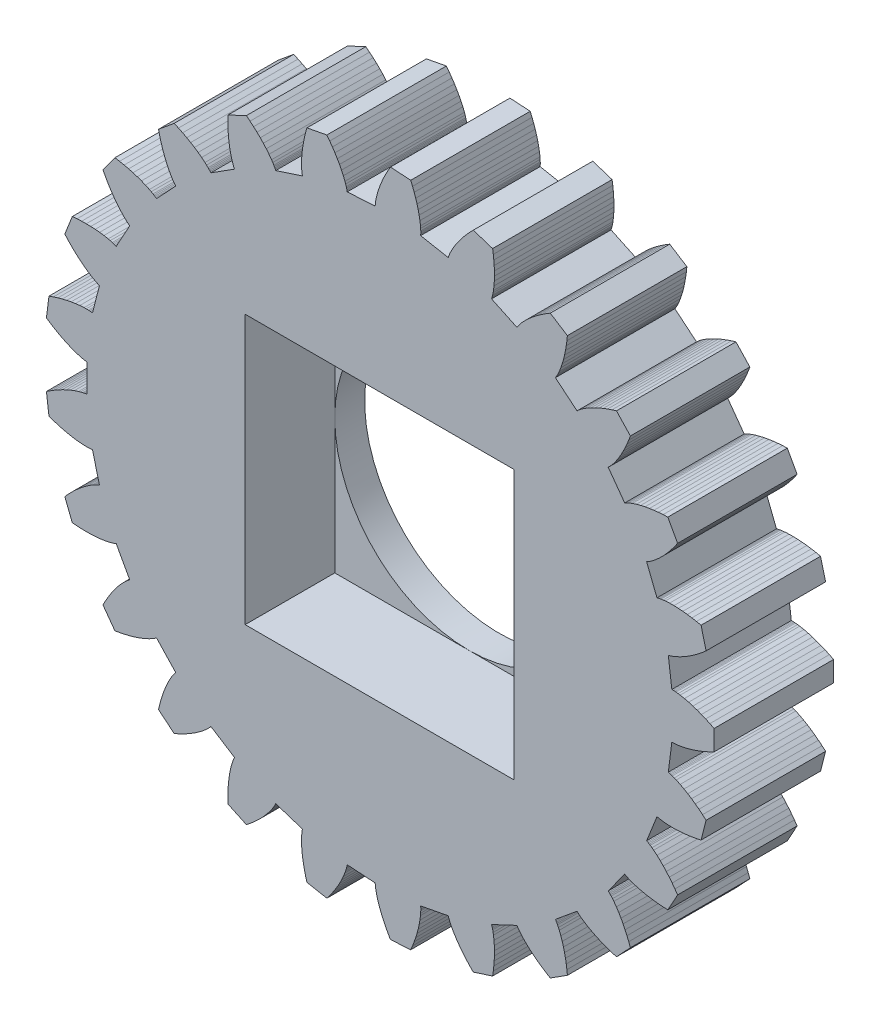
SolidWorks part; units mm, degrees
ref_plane "Front Plane" through (0, 0, 0) normal (0, 0, 1) x (1, 0, 0)
ref_plane "Top Plane" through (0, 0, 0) normal (0, 1, 0) x (1, 0, 0)
ref_plane "Right Plane" through (0, 0, 0) normal (1, 0, 0) x (0, 0, -1)
sketch "Model" plane through (0, 0, 0) normal (0, 0, 1) x (1, 0, 0)
  line L0 (22.5153, 13.4937) -> (22.5501, 13.4944)
  line L1 (22.5501, 13.4944) -> (22.5851, 13.4936)
  line L2 (22.5851, 13.4936) -> (22.6201, 13.4916)
  line L3 (22.6201, 13.4916) -> (22.6552, 13.4888)
  line L4 (22.6552, 13.4888) -> (22.7255, 13.481)
  line L5 (22.7255, 13.481) -> (22.796, 13.4706)
  line L6 (22.796, 13.4706) -> (22.9373, 13.4433)
  line L7 (22.9373, 13.4433) -> (23.079, 13.4085)
  line L8 (23.079, 13.4085) -> (23.221, 13.3669)
  line L9 (23.221, 13.3669) -> (23.363, 13.3191)
  line L10 (23.363, 13.3191) -> (23.5051, 13.2655)
  line L11 (23.5051, 13.2655) -> (23.647, 13.2062)
  line L12 (23.647, 13.2062) -> (23.7888, 13.1416)
  line L13 (23.7888, 13.1416) -> (23.9303, 13.0718)
  line L14 (23.9303, 13.0718) -> (23.9303, 12.3915)
  line L15 (23.9303, 12.3915) -> (23.7888, 12.3217)
  line L16 (23.7888, 12.3217) -> (23.647, 12.257)
  line L17 (23.647, 12.257) -> (23.5051, 12.1978)
  line L18 (23.5051, 12.1978) -> (23.363, 12.1441)
  line L19 (23.363, 12.1441) -> (23.221, 12.0963)
  line L20 (23.221, 12.0963) -> (23.079, 12.0548)
  line L21 (23.079, 12.0548) -> (22.9373, 12.0199)
  line L22 (22.9373, 12.0199) -> (22.796, 11.9927)
  line L23 (22.796, 11.9927) -> (22.7255, 11.9823)
  line L24 (22.7255, 11.9823) -> (22.6552, 11.9745)
  line L25 (22.6552, 11.9745) -> (22.6201, 11.9716)
  line L26 (22.6201, 11.9716) -> (22.5851, 11.9697)
  line L27 (22.5851, 11.9697) -> (22.5501, 11.9688)
  line L28 (22.5501, 11.9688) -> (22.5153, 11.9696)
  line L29 (22.5153, 11.9696) -> (22.3975, 11.0367)
  line L30 (22.3975, 11.0367) -> (22.4314, 11.0287)
  line L31 (22.4314, 11.0287) -> (22.465, 11.0192)
  line L32 (22.465, 11.0192) -> (22.4984, 11.0086)
  line L33 (22.4984, 11.0086) -> (22.5317, 10.9971)
  line L34 (22.5317, 10.9971) -> (22.5978, 10.9721)
  line L35 (22.5978, 10.9721) -> (22.6635, 10.9445)
  line L36 (22.6635, 10.9445) -> (22.7937, 10.8829)
  line L37 (22.7937, 10.8829) -> (22.9223, 10.8139)
  line L38 (22.9223, 10.8139) -> (23.0494, 10.7384)
  line L39 (23.0494, 10.7384) -> (23.1751, 10.6567)
  line L40 (23.1751, 10.6567) -> (23.2994, 10.5694)
  line L41 (23.2994, 10.5694) -> (23.4221, 10.4767)
  line L42 (23.4221, 10.4767) -> (23.5434, 10.3789)
  line L43 (23.5434, 10.3789) -> (23.6631, 10.2761)
  line L44 (23.6631, 10.2761) -> (23.4939, 9.6172)
  line L45 (23.4939, 9.6172) -> (23.3395, 9.5847)
  line L46 (23.3395, 9.5847) -> (23.1861, 9.5574)
  line L47 (23.1861, 9.5574) -> (23.0339, 9.5353)
  line L48 (23.0339, 9.5353) -> (22.8829, 9.5187)
  line L49 (22.8829, 9.5187) -> (22.7334, 9.5077)
  line L50 (22.7334, 9.5077) -> (22.5856, 9.5027)
  line L51 (22.5856, 9.5027) -> (22.4397, 9.5042)
  line L52 (22.4397, 9.5042) -> (22.296, 9.513)
  line L53 (22.296, 9.513) -> (22.2251, 9.5205)
  line L54 (22.2251, 9.5205) -> (22.1551, 9.5304)
  line L55 (22.1551, 9.5304) -> (22.1204, 9.5364)
  line L56 (22.1204, 9.5364) -> (22.086, 9.5432)
  line L57 (22.086, 9.5432) -> (22.0519, 9.551)
  line L58 (22.0519, 9.551) -> (22.0184, 9.5604)
  line L59 (22.0184, 9.5604) -> (21.6723, 8.6861)
  line L60 (21.6723, 8.6861) -> (21.7031, 8.67)
  line L61 (21.7031, 8.67) -> (21.7333, 8.6524)
  line L62 (21.7333, 8.6524) -> (21.7631, 8.6338)
  line L63 (21.7631, 8.6338) -> (21.7925, 8.6145)
  line L64 (21.7925, 8.6145) -> (21.8503, 8.5737)
  line L65 (21.8503, 8.5737) -> (21.9071, 8.5306)
  line L66 (21.9071, 8.5306) -> (22.0178, 8.4387)
  line L67 (22.0178, 8.4387) -> (22.1252, 8.3399)
  line L68 (22.1252, 8.3399) -> (22.2296, 8.2351)
  line L69 (22.2296, 8.2351) -> (22.331, 8.1247)
  line L70 (22.331, 8.1247) -> (22.4297, 8.0093)
  line L71 (22.4297, 8.0093) -> (22.5255, 7.889)
  line L72 (22.5255, 7.889) -> (22.6186, 7.764)
  line L73 (22.6186, 7.764) -> (22.709, 7.6347)
  line L74 (22.709, 7.6347) -> (22.3812, 7.0385)
  line L75 (22.3812, 7.0385) -> (22.2236, 7.0455)
  line L76 (22.2236, 7.0455) -> (22.0683, 7.0572)
  line L77 (22.0683, 7.0572) -> (21.9153, 7.0737)
  line L78 (21.9153, 7.0737) -> (21.765, 7.0951)
  line L79 (21.765, 7.0951) -> (21.6175, 7.1216)
  line L80 (21.6175, 7.1216) -> (21.473, 7.1536)
  line L81 (21.473, 7.1536) -> (21.3321, 7.1913)
  line L82 (21.3321, 7.1913) -> (21.1951, 7.2356)
  line L83 (21.1951, 7.2356) -> (21.1283, 7.2604)
  line L84 (21.1283, 7.2604) -> (21.0629, 7.2874)
  line L85 (21.0629, 7.2874) -> (21.0308, 7.3018)
  line L86 (21.0308, 7.3018) -> (20.9992, 7.317)
  line L87 (20.9992, 7.317) -> (20.9681, 7.3331)
  line L88 (20.9681, 7.3331) -> (20.938, 7.3505)
  line L89 (20.938, 7.3505) -> (20.3853, 6.5898)
  line L90 (20.3853, 6.5898) -> (20.4112, 6.5665)
  line L91 (20.4112, 6.5665) -> (20.4361, 6.5419)
  line L92 (20.4361, 6.5419) -> (20.4602, 6.5165)
  line L93 (20.4602, 6.5165) -> (20.4839, 6.4905)
  line L94 (20.4839, 6.4905) -> (20.5298, 6.4366)
  line L95 (20.5298, 6.4366) -> (20.574, 6.3808)
  line L96 (20.574, 6.3808) -> (20.6584, 6.2642)
  line L97 (20.6584, 6.2642) -> (20.7379, 6.1418)
  line L98 (20.7379, 6.1418) -> (20.8129, 6.0143)
  line L99 (20.8129, 6.0143) -> (20.8838, 5.8822)
  line L100 (20.8838, 5.8822) -> (20.9506, 5.7458)
  line L101 (20.9506, 5.7458) -> (21.0135, 5.6055)
  line L102 (21.0135, 5.6055) -> (21.0726, 5.4613)
  line L103 (21.0726, 5.4613) -> (21.128, 5.3136)
  line L104 (21.128, 5.3136) -> (20.6622, 4.8176)
  line L105 (20.6622, 4.8176) -> (20.5113, 4.8636)
  line L106 (20.5113, 4.8636) -> (20.3638, 4.9136)
  line L107 (20.3638, 4.9136) -> (20.2197, 4.9675)
  line L108 (20.2197, 4.9675) -> (20.0794, 5.0257)
  line L109 (20.0794, 5.0257) -> (19.9432, 5.0881)
  line L110 (19.9432, 5.0881) -> (19.8112, 5.1549)
  line L111 (19.8112, 5.1549) -> (19.6841, 5.2265)
  line L112 (19.6841, 5.2265) -> (19.5624, 5.3035)
  line L113 (19.5624, 5.3035) -> (19.5039, 5.3441)
  line L114 (19.5039, 5.3441) -> (19.4472, 5.3866)
  line L115 (19.4472, 5.3866) -> (19.4197, 5.4085)
  line L116 (19.4197, 5.4085) -> (19.3929, 5.4311)
  line L117 (19.3929, 5.4311) -> (19.3668, 5.4543)
  line L118 (19.3668, 5.4543) -> (19.3419, 5.4787)
  line L119 (19.3419, 5.4787) -> (18.6174, 4.8793)
  line L120 (18.6174, 4.8793) -> (18.6367, 4.8503)
  line L121 (18.6367, 4.8503) -> (18.6547, 4.8204)
  line L122 (18.6547, 4.8204) -> (18.6718, 4.7898)
  line L123 (18.6718, 4.7898) -> (18.6882, 4.7586)
  line L124 (18.6882, 4.7586) -> (18.7193, 4.6951)
  line L125 (18.7193, 4.6951) -> (18.7483, 4.63)
  line L126 (18.7483, 4.63) -> (18.801, 4.496)
  line L127 (18.801, 4.496) -> (18.8476, 4.3577)
  line L128 (18.8476, 4.3577) -> (18.8885, 4.2156)
  line L129 (18.8885, 4.2156) -> (18.9243, 4.07)
  line L130 (18.9243, 4.07) -> (18.9551, 3.9213)
  line L131 (18.9551, 3.9213) -> (18.9811, 3.7697)
  line L132 (18.9811, 3.7697) -> (19.0025, 3.6154)
  line L133 (19.0025, 3.6154) -> (19.0194, 3.4586)
  line L134 (19.0194, 3.4586) -> (18.445, 3.094)
  line L135 (18.445, 3.094) -> (18.3102, 3.1761)
  line L136 (18.3102, 3.1761) -> (18.1797, 3.2611)
  line L137 (18.1797, 3.2611) -> (18.0536, 3.3493)
  line L138 (18.0536, 3.3493) -> (17.9322, 3.4404)
  line L139 (17.9322, 3.4404) -> (17.8157, 3.5348)
  line L140 (17.8157, 3.5348) -> (17.7045, 3.6323)
  line L141 (17.7045, 3.6323) -> (17.5992, 3.7333)
  line L142 (17.5992, 3.7333) -> (17.5004, 3.8381)
  line L143 (17.5004, 3.8381) -> (17.4539, 3.892)
  line L144 (17.4539, 3.892) -> (17.4096, 3.9472)
  line L145 (17.4096, 3.9472) -> (17.3884, 3.9753)
  line L146 (17.3884, 3.9753) -> (17.368, 4.0038)
  line L147 (17.368, 4.0038) -> (17.3486, 4.0329)
  line L148 (17.3486, 4.0329) -> (17.3305, 4.0626)
  line L149 (17.3305, 4.0626) -> (16.4797, 3.6623)
  line L150 (16.4797, 3.6623) -> (16.4912, 3.6294)
  line L151 (16.4912, 3.6294) -> (16.5012, 3.5959)
  line L152 (16.5012, 3.5959) -> (16.5101, 3.562)
  line L153 (16.5101, 3.562) -> (16.5183, 3.5278)
  line L154 (16.5183, 3.5278) -> (16.5326, 3.4585)
  line L155 (16.5326, 3.4585) -> (16.5445, 3.3882)
  line L156 (16.5445, 3.3882) -> (16.5622, 3.2454)
  line L157 (16.5622, 3.2454) -> (16.5729, 3.0998)
  line L158 (16.5729, 3.0998) -> (16.5772, 2.952)
  line L159 (16.5772, 2.952) -> (16.5756, 2.8021)
  line L160 (16.5756, 2.8021) -> (16.5685, 2.6504)
  line L161 (16.5685, 2.6504) -> (16.556, 2.4971)
  line L162 (16.556, 2.4971) -> (16.5384, 2.3423)
  line L163 (16.5384, 2.3423) -> (16.5157, 2.1862)
  line L164 (16.5157, 2.1862) -> (15.8687, 1.9759)
  line L165 (15.8687, 1.9759) -> (15.7586, 2.0889)
  line L166 (15.7586, 2.0889) -> (15.6533, 2.2038)
  line L167 (15.6533, 2.2038) -> (15.5531, 2.3205)
  line L168 (15.5531, 2.3205) -> (15.4582, 2.439)
  line L169 (15.4582, 2.439) -> (15.3688, 2.5593)
  line L170 (15.3688, 2.5593) -> (15.2854, 2.6815)
  line L171 (15.2854, 2.6815) -> (15.2085, 2.8055)
  line L172 (15.2085, 2.8055) -> (15.1389, 2.9315)
  line L173 (15.1389, 2.9315) -> (15.1072, 2.9954)
  line L174 (15.1072, 2.9954) -> (15.078, 3.0598)
  line L175 (15.078, 3.0598) -> (15.0645, 3.0923)
  line L176 (15.0645, 3.0923) -> (15.0519, 3.125)
  line L177 (15.0519, 3.125) -> (15.0402, 3.158)
  line L178 (15.0402, 3.158) -> (15.0302, 3.1913)
  line L179 (15.0302, 3.1913) -> (14.1065, 3.0151)
  line L180 (14.1065, 3.0151) -> (14.1095, 2.9804)
  line L181 (14.1095, 2.9804) -> (14.1108, 2.9455)
  line L182 (14.1108, 2.9455) -> (14.111, 2.9104)
  line L183 (14.111, 2.9104) -> (14.1104, 2.8752)
  line L184 (14.1104, 2.8752) -> (14.107, 2.8046)
  line L185 (14.107, 2.8046) -> (14.1011, 2.7336)
  line L186 (14.1011, 2.7336) -> (14.0827, 2.5908)
  line L187 (14.0827, 2.5908) -> (14.0569, 2.4471)
  line L188 (14.0569, 2.4471) -> (14.0243, 2.3029)
  line L189 (14.0243, 2.3029) -> (13.9855, 2.1581)
  line L190 (13.9855, 2.1581) -> (13.9409, 2.0129)
  line L191 (13.9409, 2.0129) -> (13.8907, 1.8675)
  line L192 (13.8907, 1.8675) -> (13.8351, 1.722)
  line L193 (13.8351, 1.722) -> (13.7743, 1.5764)
  line L194 (13.7743, 1.5764) -> (13.0953, 1.5337)
  line L195 (13.0953, 1.5337) -> (13.0168, 1.6705)
  line L196 (13.0168, 1.6705) -> (12.9434, 1.808)
  line L197 (12.9434, 1.808) -> (12.8753, 1.9459)
  line L198 (12.8753, 1.9459) -> (12.8128, 2.0843)
  line L199 (12.8128, 2.0843) -> (12.7562, 2.2231)
  line L200 (12.7562, 2.2231) -> (12.7058, 2.3621)
  line L201 (12.7058, 2.3621) -> (12.6622, 2.5014)
  line L202 (12.6622, 2.5014) -> (12.6261, 2.6408)
  line L203 (12.6261, 2.6408) -> (12.6113, 2.7105)
  line L204 (12.6113, 2.7105) -> (12.599, 2.7801)
  line L205 (12.599, 2.7801) -> (12.594, 2.815)
  line L206 (12.594, 2.815) -> (12.5899, 2.8498)
  line L207 (12.5899, 2.8498) -> (12.5868, 2.8846)
  line L208 (12.5868, 2.8846) -> (12.5854, 2.9194)
  line L209 (12.5854, 2.9194) -> (11.6469, 2.9784)
  line L210 (11.6469, 2.9784) -> (11.6411, 2.9441)
  line L211 (11.6411, 2.9441) -> (11.6337, 2.91)
  line L212 (11.6337, 2.91) -> (11.6253, 2.8759)
  line L213 (11.6253, 2.8759) -> (11.6159, 2.842)
  line L214 (11.6159, 2.842) -> (11.595, 2.7744)
  line L215 (11.595, 2.7744) -> (11.5716, 2.7071)
  line L216 (11.5716, 2.7071) -> (11.5184, 2.5733)
  line L217 (11.5184, 2.5733) -> (11.4576, 2.4407)
  line L218 (11.4576, 2.4407) -> (11.3902, 2.309)
  line L219 (11.3902, 2.309) -> (11.3166, 2.1784)
  line L220 (11.3166, 2.1784) -> (11.2372, 2.049)
  line L221 (11.2372, 2.049) -> (11.1525, 1.9206)
  line L222 (11.1525, 1.9206) -> (11.0624, 1.7935)
  line L223 (11.0624, 1.7935) -> (10.9673, 1.6676)
  line L224 (10.9673, 1.6676) -> (10.2991, 1.7951)
  line L225 (10.2991, 1.7951) -> (10.257, 1.9471)
  line L226 (10.257, 1.9471) -> (10.2201, 2.0985)
  line L227 (10.2201, 2.0985) -> (10.1885, 2.249)
  line L228 (10.1885, 2.249) -> (10.1624, 2.3986)
  line L229 (10.1624, 2.3986) -> (10.1421, 2.5471)
  line L230 (10.1421, 2.5471) -> (10.1278, 2.6943)
  line L231 (10.1278, 2.6943) -> (10.1202, 2.8401)
  line L232 (10.1202, 2.8401) -> (10.1199, 2.984)
  line L233 (10.1199, 2.984) -> (10.1229, 3.0552)
  line L234 (10.1229, 3.0552) -> (10.1284, 3.1258)
  line L235 (10.1284, 3.1258) -> (10.1322, 3.1607)
  line L236 (10.1322, 3.1607) -> (10.1368, 3.1955)
  line L237 (10.1368, 3.1955) -> (10.1425, 3.23)
  line L238 (10.1425, 3.23) -> (10.1498, 3.264)
  line L239 (10.1498, 3.264) -> (9.2555, 3.5546)
  line L240 (9.2555, 3.5546) -> (9.2413, 3.5228)
  line L241 (9.2413, 3.5228) -> (9.2257, 3.4916)
  line L242 (9.2257, 3.4916) -> (9.209, 3.4607)
  line L243 (9.209, 3.4607) -> (9.1915, 3.4302)
  line L244 (9.1915, 3.4302) -> (9.1545, 3.3699)
  line L245 (9.1545, 3.3699) -> (9.1151, 3.3105)
  line L246 (9.1151, 3.3105) -> (9.0302, 3.1942)
  line L247 (9.0302, 3.1942) -> (8.9384, 3.0808)
  line L248 (8.9384, 3.0808) -> (8.8403, 2.9701)
  line L249 (8.8403, 2.9701) -> (8.7366, 2.8619)
  line L250 (8.7366, 2.8619) -> (8.6275, 2.7562)
  line L251 (8.6275, 2.7562) -> (8.5135, 2.653)
  line L252 (8.5135, 2.653) -> (8.3947, 2.5522)
  line L253 (8.3947, 2.5522) -> (8.2713, 2.4539)
  line L254 (8.2713, 2.4539) -> (7.6557, 2.7436)
  line L255 (7.6557, 2.7436) -> (7.6528, 2.9013)
  line L256 (7.6528, 2.9013) -> (7.6547, 3.0571)
  line L257 (7.6547, 3.0571) -> (7.6615, 3.2108)
  line L258 (7.6615, 3.2108) -> (7.6734, 3.3622)
  line L259 (7.6734, 3.3622) -> (7.6906, 3.5111)
  line L260 (7.6906, 3.5111) -> (7.7135, 3.6572)
  line L261 (7.7135, 3.6572) -> (7.7423, 3.8003)
  line L262 (7.7423, 3.8003) -> (7.7778, 3.9398)
  line L263 (7.7778, 3.9398) -> (7.7984, 4.008)
  line L264 (7.7984, 4.008) -> (7.8213, 4.0749)
  line L265 (7.8213, 4.0749) -> (7.8337, 4.1079)
  line L266 (7.8337, 4.1079) -> (7.8468, 4.1404)
  line L267 (7.8468, 4.1404) -> (7.8609, 4.1724)
  line L268 (7.8609, 4.1724) -> (7.8764, 4.2036)
  line L269 (7.8764, 4.2036) -> (7.0825, 4.7074)
  line L270 (7.0825, 4.7074) -> (7.0608, 4.6801)
  line L271 (7.0608, 4.6801) -> (7.0379, 4.6537)
  line L272 (7.0379, 4.6537) -> (7.0141, 4.628)
  line L273 (7.0141, 4.628) -> (6.9896, 4.6028)
  line L274 (6.9896, 4.6028) -> (6.9387, 4.5536)
  line L275 (6.9387, 4.5536) -> (6.8858, 4.5059)
  line L276 (6.8858, 4.5059) -> (6.7746, 4.4144)
  line L277 (6.7746, 4.4144) -> (6.6575, 4.3274)
  line L278 (6.6575, 4.3274) -> (6.535, 4.2445)
  line L279 (6.535, 4.2445) -> (6.4076, 4.1655)
  line L280 (6.4076, 4.1655) -> (6.2757, 4.0903)
  line L281 (6.2757, 4.0903) -> (6.1395, 4.0186)
  line L282 (6.1395, 4.0186) -> (5.9994, 3.9506)
  line L283 (5.9994, 3.9506) -> (5.8554, 3.8861)
  line L284 (5.8554, 3.8861) -> (5.3312, 4.3197)
  line L285 (5.3312, 4.3197) -> (5.3676, 4.4732)
  line L286 (5.3676, 4.4732) -> (5.4082, 4.6237)
  line L287 (5.4082, 4.6237) -> (5.453, 4.7708)
  line L288 (5.453, 4.7708) -> (5.5022, 4.9145)
  line L289 (5.5022, 4.9145) -> (5.556, 5.0544)
  line L290 (5.556, 5.0544) -> (5.6144, 5.1903)
  line L291 (5.6144, 5.1903) -> (5.6779, 5.3217)
  line L292 (5.6779, 5.3217) -> (5.747, 5.4479)
  line L293 (5.747, 5.4479) -> (5.7839, 5.5089)
  line L294 (5.7839, 5.5089) -> (5.8227, 5.5681)
  line L295 (5.8227, 5.5681) -> (5.8429, 5.5969)
  line L296 (5.8429, 5.5969) -> (5.8637, 5.6251)
  line L297 (5.8637, 5.6251) -> (5.8853, 5.6526)
  line L298 (5.8853, 5.6526) -> (5.9081, 5.6789)
  line L299 (5.9081, 5.6789) -> (5.2644, 6.3644)
  line L300 (5.2644, 6.3644) -> (5.2367, 6.3433)
  line L301 (5.2367, 6.3433) -> (5.2079, 6.3235)
  line L302 (5.2079, 6.3235) -> (5.1784, 6.3045)
  line L303 (5.1784, 6.3045) -> (5.1484, 6.2862)
  line L304 (5.1484, 6.2862) -> (5.0869, 6.2512)
  line L305 (5.0869, 6.2512) -> (5.0238, 6.2181)
  line L306 (5.0238, 6.2181) -> (4.8934, 6.1571)
  line L307 (4.8934, 6.1571) -> (4.7583, 6.102)
  line L308 (4.7583, 6.102) -> (4.619, 6.0522)
  line L309 (4.619, 6.0522) -> (4.476, 6.0074)
  line L310 (4.476, 6.0074) -> (4.3295, 5.9673)
  line L311 (4.3295, 5.9673) -> (4.1798, 5.9318)
  line L312 (4.1798, 5.9318) -> (4.0272, 5.9007)
  line L313 (4.0272, 5.9007) -> (3.8717, 5.874)
  line L314 (3.8717, 5.874) -> (3.4718, 6.4244)
  line L315 (3.4718, 6.4244) -> (3.5452, 6.5641)
  line L316 (3.5452, 6.5641) -> (3.6219, 6.6996)
  line L317 (3.6219, 6.6996) -> (3.7019, 6.831)
  line L318 (3.7019, 6.831) -> (3.7853, 6.9579)
  line L319 (3.7853, 6.9579) -> (3.8721, 7.0801)
  line L320 (3.8721, 7.0801) -> (3.9625, 7.1972)
  line L321 (3.9625, 7.1972) -> (4.0567, 7.3086)
  line L322 (4.0567, 7.3086) -> (4.1551, 7.4138)
  line L323 (4.1551, 7.4138) -> (4.206, 7.4636)
  line L324 (4.206, 7.4636) -> (4.2583, 7.5113)
  line L325 (4.2583, 7.5113) -> (4.285, 7.5342)
  line L326 (4.285, 7.5342) -> (4.3122, 7.5563)
  line L327 (4.3122, 7.5563) -> (4.3399, 7.5776)
  line L328 (4.3399, 7.5776) -> (4.3685, 7.5975)
  line L329 (4.3685, 7.5975) -> (3.9155, 8.4215)
  line L330 (3.9155, 8.4215) -> (3.8834, 8.4079)
  line L331 (3.8834, 8.4079) -> (3.8506, 8.3959)
  line L332 (3.8506, 8.3959) -> (3.8174, 8.3848)
  line L333 (3.8174, 8.3848) -> (3.7837, 8.3745)
  line L334 (3.7837, 8.3745) -> (3.7154, 8.3559)
  line L335 (3.7154, 8.3559) -> (3.6461, 8.3396)
  line L336 (3.6461, 8.3396) -> (3.5046, 8.3129)
  line L337 (3.5046, 8.3129) -> (3.36, 8.2932)
  line L338 (3.36, 8.2932) -> (3.2127, 8.2796)
  line L339 (3.2127, 8.2796) -> (3.0631, 8.2717)
  line L340 (3.0631, 8.2717) -> (2.9112, 8.2693)
  line L341 (2.9112, 8.2693) -> (2.7574, 8.2721)
  line L342 (2.7574, 8.2721) -> (2.6018, 8.28)
  line L343 (2.6018, 8.28) -> (2.4446, 8.2928)
  line L344 (2.4446, 8.2928) -> (2.1941, 8.9254)
  line L345 (2.1941, 8.9254) -> (2.3, 9.0424)
  line L346 (2.3, 9.0424) -> (2.408, 9.1547)
  line L347 (2.408, 9.1547) -> (2.5182, 9.262)
  line L348 (2.5182, 9.262) -> (2.6305, 9.3642)
  line L349 (2.6305, 9.3642) -> (2.745, 9.4609)
  line L350 (2.745, 9.4609) -> (2.8617, 9.5518)
  line L351 (2.8617, 9.5518) -> (2.9806, 9.6364)
  line L352 (2.9806, 9.6364) -> (3.102, 9.7138)
  line L353 (3.102, 9.7138) -> (3.1637, 9.7494)
  line L354 (3.1637, 9.7494) -> (3.2262, 9.7825)
  line L355 (3.2262, 9.7825) -> (3.2578, 9.7981)
  line L356 (3.2578, 9.7981) -> (3.2897, 9.8128)
  line L357 (3.2897, 9.8128) -> (3.3218, 9.8265)
  line L358 (3.3218, 9.8265) -> (3.3544, 9.8386)
  line L359 (3.3544, 9.8386) -> (3.1206, 10.7493)
  line L360 (3.1206, 10.7493) -> (3.0862, 10.7442)
  line L361 (3.0862, 10.7442) -> (3.0514, 10.7407)
  line L362 (3.0514, 10.7407) -> (3.0164, 10.7383)
  line L363 (3.0164, 10.7383) -> (2.9813, 10.7367)
  line L364 (2.9813, 10.7367) -> (2.9105, 10.7356)
  line L365 (2.9105, 10.7356) -> (2.8393, 10.7371)
  line L366 (2.8393, 10.7371) -> (2.6956, 10.7464)
  line L367 (2.6956, 10.7464) -> (2.5506, 10.7632)
  line L368 (2.5506, 10.7632) -> (2.4046, 10.7867)
  line L369 (2.4046, 10.7867) -> (2.2577, 10.8163)
  line L370 (2.2577, 10.8163) -> (2.11, 10.8517)
  line L371 (2.11, 10.8517) -> (1.9618, 10.8927)
  line L372 (1.9618, 10.8927) -> (1.813, 10.9391)
  line L373 (1.813, 10.9391) -> (1.6639, 10.9906)
  line L374 (1.6639, 10.9906) -> (1.5786, 11.6655)
  line L375 (1.5786, 11.6655) -> (1.7103, 11.7525)
  line L376 (1.7103, 11.7525) -> (1.8428, 11.8344)
  line L377 (1.8428, 11.8344) -> (1.9762, 11.911)
  line L378 (1.9762, 11.911) -> (2.1104, 11.982)
  line L379 (2.1104, 11.982) -> (2.2454, 12.0472)
  line L380 (2.2454, 12.0472) -> (2.381, 12.1063)
  line L381 (2.381, 12.1063) -> (2.5172, 12.1586)
  line L382 (2.5172, 12.1586) -> (2.654, 12.2034)
  line L383 (2.654, 12.2034) -> (2.7227, 12.2225)
  line L384 (2.7227, 12.2225) -> (2.7915, 12.2391)
  line L385 (2.7915, 12.2391) -> (2.8259, 12.2463)
  line L386 (2.8259, 12.2463) -> (2.8604, 12.2526)
  line L387 (2.8604, 12.2526) -> (2.8949, 12.2578)
  line L388 (2.8949, 12.2578) -> (2.9296, 12.2615)
  line L389 (2.9296, 12.2615) -> (2.9296, 13.2018)
  line L390 (2.9296, 13.2018) -> (2.8949, 13.2054)
  line L391 (2.8949, 13.2054) -> (2.8604, 13.2107)
  line L392 (2.8604, 13.2107) -> (2.8259, 13.217)
  line L393 (2.8259, 13.217) -> (2.7915, 13.2242)
  line L394 (2.7915, 13.2242) -> (2.7227, 13.2408)
  line L395 (2.7227, 13.2408) -> (2.654, 13.2599)
  line L396 (2.654, 13.2599) -> (2.5172, 13.3047)
  line L397 (2.5172, 13.3047) -> (2.381, 13.357)
  line L398 (2.381, 13.357) -> (2.2454, 13.416)
  line L399 (2.2454, 13.416) -> (2.1104, 13.4812)
  line L400 (2.1104, 13.4812) -> (1.9762, 13.5523)
  line L401 (1.9762, 13.5523) -> (1.8428, 13.6289)
  line L402 (1.8428, 13.6289) -> (1.7103, 13.7107)
  line L403 (1.7103, 13.7107) -> (1.5786, 13.7977)
  line L404 (1.5786, 13.7977) -> (1.6639, 14.4727)
  line L405 (1.6639, 14.4727) -> (1.813, 14.5242)
  line L406 (1.813, 14.5242) -> (1.9618, 14.5705)
  line L407 (1.9618, 14.5705) -> (2.11, 14.6115)
  line L408 (2.11, 14.6115) -> (2.2577, 14.647)
  line L409 (2.2577, 14.647) -> (2.4046, 14.6766)
  line L410 (2.4046, 14.6766) -> (2.5506, 14.7)
  line L411 (2.5506, 14.7) -> (2.6956, 14.7168)
  line L412 (2.6956, 14.7168) -> (2.8393, 14.7261)
  line L413 (2.8393, 14.7261) -> (2.9105, 14.7276)
  line L414 (2.9105, 14.7276) -> (2.9813, 14.7266)
  line L415 (2.9813, 14.7266) -> (3.0164, 14.725)
  line L416 (3.0164, 14.725) -> (3.0514, 14.7225)
  line L417 (3.0514, 14.7225) -> (3.0862, 14.719)
  line L418 (3.0862, 14.719) -> (3.1206, 14.7139)
  line L419 (3.1206, 14.7139) -> (3.3544, 15.6247)
  line L420 (3.3544, 15.6247) -> (3.3218, 15.6368)
  line L421 (3.3218, 15.6368) -> (3.2897, 15.6505)
  line L422 (3.2897, 15.6505) -> (3.2578, 15.6652)
  line L423 (3.2578, 15.6652) -> (3.2262, 15.6807)
  line L424 (3.2262, 15.6807) -> (3.1637, 15.7139)
  line L425 (3.1637, 15.7139) -> (3.102, 15.7495)
  line L426 (3.102, 15.7495) -> (2.9806, 15.8269)
  line L427 (2.9806, 15.8269) -> (2.8617, 15.9114)
  line L428 (2.8617, 15.9114) -> (2.745, 16.0023)
  line L429 (2.745, 16.0023) -> (2.6305, 16.0991)
  line L430 (2.6305, 16.0991) -> (2.5182, 16.2013)
  line L431 (2.5182, 16.2013) -> (2.408, 16.3086)
  line L432 (2.408, 16.3086) -> (2.3, 16.4209)
  line L433 (2.3, 16.4209) -> (2.1941, 16.5379)
  line L434 (2.1941, 16.5379) -> (2.4446, 17.1704)
  line L435 (2.4446, 17.1704) -> (2.6018, 17.1832)
  line L436 (2.6018, 17.1832) -> (2.7574, 17.1911)
  line L437 (2.7574, 17.1911) -> (2.9112, 17.1939)
  line L438 (2.9112, 17.1939) -> (3.0631, 17.1915)
  line L439 (3.0631, 17.1915) -> (3.2127, 17.1837)
  line L440 (3.2127, 17.1837) -> (3.36, 17.1701)
  line L441 (3.36, 17.1701) -> (3.5046, 17.1503)
  line L442 (3.5046, 17.1503) -> (3.6461, 17.1236)
  line L443 (3.6461, 17.1236) -> (3.7154, 17.1073)
  line L444 (3.7154, 17.1073) -> (3.7837, 17.0887)
  line L445 (3.7837, 17.0887) -> (3.8174, 17.0784)
  line L446 (3.8174, 17.0784) -> (3.8506, 17.0674)
  line L447 (3.8506, 17.0674) -> (3.8834, 17.0553)
  line L448 (3.8834, 17.0553) -> (3.9155, 17.0418)
  line L449 (3.9155, 17.0418) -> (4.3685, 17.8658)
  line L450 (4.3685, 17.8658) -> (4.3399, 17.8857)
  line L451 (4.3399, 17.8857) -> (4.3122, 17.9069)
  line L452 (4.3122, 17.9069) -> (4.285, 17.9291)
  line L453 (4.285, 17.9291) -> (4.2583, 17.952)
  line L454 (4.2583, 17.952) -> (4.206, 17.9996)
  line L455 (4.206, 17.9996) -> (4.1551, 18.0495)
  line L456 (4.1551, 18.0495) -> (4.0567, 18.1546)
  line L457 (4.0567, 18.1546) -> (3.9625, 18.2661)
  line L458 (3.9625, 18.2661) -> (3.8721, 18.3831)
  line L459 (3.8721, 18.3831) -> (3.7853, 18.5053)
  line L460 (3.7853, 18.5053) -> (3.7019, 18.6322)
  line L461 (3.7019, 18.6322) -> (3.6219, 18.7636)
  line L462 (3.6219, 18.7636) -> (3.5452, 18.8992)
  line L463 (3.5452, 18.8992) -> (3.4718, 19.0388)
  line L464 (3.4718, 19.0388) -> (3.8717, 19.5892)
  line L465 (3.8717, 19.5892) -> (4.0272, 19.5626)
  line L466 (4.0272, 19.5626) -> (4.1798, 19.5315)
  line L467 (4.1798, 19.5315) -> (4.3295, 19.496)
  line L468 (4.3295, 19.496) -> (4.476, 19.4559)
  line L469 (4.476, 19.4559) -> (4.619, 19.4111)
  line L470 (4.619, 19.4111) -> (4.7583, 19.3613)
  line L471 (4.7583, 19.3613) -> (4.8934, 19.3062)
  line L472 (4.8934, 19.3062) -> (5.0238, 19.2451)
  line L473 (5.0238, 19.2451) -> (5.0869, 19.2121)
  line L474 (5.0869, 19.2121) -> (5.1484, 19.1771)
  line L475 (5.1484, 19.1771) -> (5.1784, 19.1588)
  line L476 (5.1784, 19.1588) -> (5.2079, 19.1398)
  line L477 (5.2079, 19.1398) -> (5.2367, 19.1199)
  line L478 (5.2367, 19.1199) -> (5.2644, 19.0989)
  line L479 (5.2644, 19.0989) -> (5.9081, 19.7843)
  line L480 (5.9081, 19.7843) -> (5.8853, 19.8107)
  line L481 (5.8853, 19.8107) -> (5.8637, 19.8381)
  line L482 (5.8637, 19.8381) -> (5.8429, 19.8664)
  line L483 (5.8429, 19.8664) -> (5.8227, 19.8952)
  line L484 (5.8227, 19.8952) -> (5.7839, 19.9544)
  line L485 (5.7839, 19.9544) -> (5.747, 20.0153)
  line L486 (5.747, 20.0153) -> (5.6779, 20.1416)
  line L487 (5.6779, 20.1416) -> (5.6144, 20.273)
  line L488 (5.6144, 20.273) -> (5.556, 20.4089)
  line L489 (5.556, 20.4089) -> (5.5022, 20.5488)
  line L490 (5.5022, 20.5488) -> (5.453, 20.6925)
  line L491 (5.453, 20.6925) -> (5.4082, 20.8396)
  line L492 (5.4082, 20.8396) -> (5.3676, 20.99)
  line L493 (5.3676, 20.99) -> (5.3312, 21.1435)
  line L494 (5.3312, 21.1435) -> (5.8554, 21.5772)
  line L495 (5.8554, 21.5772) -> (5.9994, 21.5127)
  line L496 (5.9994, 21.5127) -> (6.1395, 21.4446)
  line L497 (6.1395, 21.4446) -> (6.2757, 21.373)
  line L498 (6.2757, 21.373) -> (6.4076, 21.2977)
  line L499 (6.4076, 21.2977) -> (6.535, 21.2188)
  line L500 (6.535, 21.2188) -> (6.6575, 21.1359)
  line L501 (6.6575, 21.1359) -> (6.7746, 21.0489)
  line L502 (6.7746, 21.0489) -> (6.8858, 20.9574)
  line L503 (6.8858, 20.9574) -> (6.9387, 20.9097)
  line L504 (6.9387, 20.9097) -> (6.9896, 20.8605)
  line L505 (6.9896, 20.8605) -> (7.0141, 20.8352)
  line L506 (7.0141, 20.8352) -> (7.0379, 20.8095)
  line L507 (7.0379, 20.8095) -> (7.0608, 20.7831)
  line L508 (7.0608, 20.7831) -> (7.0825, 20.7559)
  line L509 (7.0825, 20.7559) -> (7.8764, 21.2597)
  line L510 (7.8764, 21.2597) -> (7.8609, 21.2909)
  line L511 (7.8609, 21.2909) -> (7.8468, 21.3229)
  line L512 (7.8468, 21.3229) -> (7.8337, 21.3554)
  line L513 (7.8337, 21.3554) -> (7.8213, 21.3883)
  line L514 (7.8213, 21.3883) -> (7.7984, 21.4553)
  line L515 (7.7984, 21.4553) -> (7.7778, 21.5235)
  line L516 (7.7778, 21.5235) -> (7.7423, 21.663)
  line L517 (7.7423, 21.663) -> (7.7135, 21.806)
  line L518 (7.7135, 21.806) -> (7.6906, 21.9522)
  line L519 (7.6906, 21.9522) -> (7.6734, 22.1011)
  line L520 (7.6734, 22.1011) -> (7.6615, 22.2525)
  line L521 (7.6615, 22.2525) -> (7.6547, 22.4061)
  line L522 (7.6547, 22.4061) -> (7.6528, 22.5619)
  line L523 (7.6528, 22.5619) -> (7.6557, 22.7196)
  line L524 (7.6557, 22.7196) -> (8.2713, 23.0093)
  line L525 (8.2713, 23.0093) -> (8.3947, 22.911)
  line L526 (8.3947, 22.911) -> (8.5135, 22.8103)
  line L527 (8.5135, 22.8103) -> (8.6275, 22.707)
  line L528 (8.6275, 22.707) -> (8.7366, 22.6013)
  line L529 (8.7366, 22.6013) -> (8.8403, 22.4932)
  line L530 (8.8403, 22.4932) -> (8.9384, 22.3824)
  line L531 (8.9384, 22.3824) -> (9.0302, 22.269)
  line L532 (9.0302, 22.269) -> (9.1151, 22.1527)
  line L533 (9.1151, 22.1527) -> (9.1545, 22.0934)
  line L534 (9.1545, 22.0934) -> (9.1915, 22.0331)
  line L535 (9.1915, 22.0331) -> (9.209, 22.0026)
  line L536 (9.209, 22.0026) -> (9.2257, 21.9717)
  line L537 (9.2257, 21.9717) -> (9.2413, 21.9405)
  line L538 (9.2413, 21.9405) -> (9.2555, 21.9086)
  line L539 (9.2555, 21.9086) -> (10.1498, 22.1992)
  line L540 (10.1498, 22.1992) -> (10.1425, 22.2333)
  line L541 (10.1425, 22.2333) -> (10.1368, 22.2677)
  line L542 (10.1368, 22.2677) -> (10.1322, 22.3025)
  line L543 (10.1322, 22.3025) -> (10.1284, 22.3375)
  line L544 (10.1284, 22.3375) -> (10.1229, 22.408)
  line L545 (10.1229, 22.408) -> (10.1199, 22.4792)
  line L546 (10.1199, 22.4792) -> (10.1202, 22.6232)
  line L547 (10.1202, 22.6232) -> (10.1278, 22.7689)
  line L548 (10.1278, 22.7689) -> (10.1421, 22.9161)
  line L549 (10.1421, 22.9161) -> (10.1624, 23.0646)
  line L550 (10.1624, 23.0646) -> (10.1885, 23.2142)
  line L551 (10.1885, 23.2142) -> (10.2201, 23.3648)
  line L552 (10.2201, 23.3648) -> (10.257, 23.5161)
  line L553 (10.257, 23.5161) -> (10.2991, 23.6682)
  line L554 (10.2991, 23.6682) -> (10.9673, 23.7957)
  line L555 (10.9673, 23.7957) -> (11.0624, 23.6698)
  line L556 (11.0624, 23.6698) -> (11.1525, 23.5426)
  line L557 (11.1525, 23.5426) -> (11.2372, 23.4143)
  line L558 (11.2372, 23.4143) -> (11.3166, 23.2848)
  line L559 (11.3166, 23.2848) -> (11.3902, 23.1542)
  line L560 (11.3902, 23.1542) -> (11.4576, 23.0226)
  line L561 (11.4576, 23.0226) -> (11.5184, 22.8899)
  line L562 (11.5184, 22.8899) -> (11.5716, 22.7562)
  line L563 (11.5716, 22.7562) -> (11.595, 22.6889)
  line L564 (11.595, 22.6889) -> (11.6159, 22.6213)
  line L565 (11.6159, 22.6213) -> (11.6253, 22.5873)
  line L566 (11.6253, 22.5873) -> (11.6337, 22.5533)
  line L567 (11.6337, 22.5533) -> (11.6411, 22.5191)
  line L568 (11.6411, 22.5191) -> (11.6469, 22.4848)
  line L569 (11.6469, 22.4848) -> (12.5854, 22.5439)
  line L570 (12.5854, 22.5439) -> (12.5868, 22.5786)
  line L571 (12.5868, 22.5786) -> (12.5899, 22.6135)
  line L572 (12.5899, 22.6135) -> (12.594, 22.6483)
  line L573 (12.594, 22.6483) -> (12.599, 22.6831)
  line L574 (12.599, 22.6831) -> (12.6113, 22.7528)
  line L575 (12.6113, 22.7528) -> (12.6261, 22.8225)
  line L576 (12.6261, 22.8225) -> (12.6622, 22.9619)
  line L577 (12.6622, 22.9619) -> (12.7058, 23.1011)
  line L578 (12.7058, 23.1011) -> (12.7562, 23.2402)
  line L579 (12.7562, 23.2402) -> (12.8128, 23.3789)
  line L580 (12.8128, 23.3789) -> (12.8753, 23.5174)
  line L581 (12.8753, 23.5174) -> (12.9434, 23.6553)
  line L582 (12.9434, 23.6553) -> (13.0168, 23.7927)
  line L583 (13.0168, 23.7927) -> (13.0953, 23.9296)
  line L584 (13.0953, 23.9296) -> (13.7743, 23.8868)
  line L585 (13.7743, 23.8868) -> (13.8351, 23.7412)
  line L586 (13.8351, 23.7412) -> (13.8907, 23.5957)
  line L587 (13.8907, 23.5957) -> (13.9409, 23.4503)
  line L588 (13.9409, 23.4503) -> (13.9855, 23.3052)
  line L589 (13.9855, 23.3052) -> (14.0243, 23.1604)
  line L590 (14.0243, 23.1604) -> (14.0569, 23.0161)
  line L591 (14.0569, 23.0161) -> (14.0827, 22.8725)
  line L592 (14.0827, 22.8725) -> (14.1011, 22.7297)
  line L593 (14.1011, 22.7297) -> (14.107, 22.6587)
  line L594 (14.107, 22.6587) -> (14.1104, 22.588)
  line L595 (14.1104, 22.588) -> (14.111, 22.5528)
  line L596 (14.111, 22.5528) -> (14.1108, 22.5178)
  line L597 (14.1108, 22.5178) -> (14.1095, 22.4828)
  line L598 (14.1095, 22.4828) -> (14.1065, 22.4482)
  line L599 (14.1065, 22.4482) -> (15.0302, 22.272)
  line L600 (15.0302, 22.272) -> (15.0402, 22.3053)
  line L601 (15.0402, 22.3053) -> (15.0519, 22.3382)
  line L602 (15.0519, 22.3382) -> (15.0645, 22.3709)
  line L603 (15.0645, 22.3709) -> (15.078, 22.4034)
  line L604 (15.078, 22.4034) -> (15.1072, 22.4679)
  line L605 (15.1072, 22.4679) -> (15.1389, 22.5317)
  line L606 (15.1389, 22.5317) -> (15.2085, 22.6577)
  line L607 (15.2085, 22.6577) -> (15.2854, 22.7818)
  line L608 (15.2854, 22.7818) -> (15.3688, 22.9039)
  line L609 (15.3688, 22.9039) -> (15.4582, 23.0242)
  line L610 (15.4582, 23.0242) -> (15.5531, 23.1428)
  line L611 (15.5531, 23.1428) -> (15.6533, 23.2595)
  line L612 (15.6533, 23.2595) -> (15.7586, 23.3743)
  line L613 (15.7586, 23.3743) -> (15.8687, 23.4873)
  line L614 (15.8687, 23.4873) -> (16.5157, 23.2771)
  line L615 (16.5157, 23.2771) -> (16.5384, 23.1209)
  line L616 (16.5384, 23.1209) -> (16.556, 22.9662)
  line L617 (16.556, 22.9662) -> (16.5685, 22.8128)
  line L618 (16.5685, 22.8128) -> (16.5756, 22.6612)
  line L619 (16.5756, 22.6612) -> (16.5772, 22.5113)
  line L620 (16.5772, 22.5113) -> (16.5729, 22.3634)
  line L621 (16.5729, 22.3634) -> (16.5622, 22.2179)
  line L622 (16.5622, 22.2179) -> (16.5445, 22.075)
  line L623 (16.5445, 22.075) -> (16.5326, 22.0048)
  line L624 (16.5326, 22.0048) -> (16.5183, 21.9355)
  line L625 (16.5183, 21.9355) -> (16.5101, 21.9012)
  line L626 (16.5101, 21.9012) -> (16.5012, 21.8673)
  line L627 (16.5012, 21.8673) -> (16.4912, 21.8338)
  line L628 (16.4912, 21.8338) -> (16.4797, 21.801)
  line L629 (16.4797, 21.801) -> (17.3305, 21.4006)
  line L630 (17.3305, 21.4006) -> (17.3486, 21.4304)
  line L631 (17.3486, 21.4304) -> (17.368, 21.4594)
  line L632 (17.368, 21.4594) -> (17.3884, 21.4879)
  line L633 (17.3884, 21.4879) -> (17.4096, 21.5161)
  line L634 (17.4096, 21.5161) -> (17.4539, 21.5712)
  line L635 (17.4539, 21.5712) -> (17.5004, 21.6252)
  line L636 (17.5004, 21.6252) -> (17.5992, 21.7299)
  line L637 (17.5992, 21.7299) -> (17.7045, 21.8309)
  line L638 (17.7045, 21.8309) -> (17.8157, 21.9285)
  line L639 (17.8157, 21.9285) -> (17.9322, 22.0228)
  line L640 (17.9322, 22.0228) -> (18.0536, 22.114)
  line L641 (18.0536, 22.114) -> (18.1797, 22.2021)
  line L642 (18.1797, 22.2021) -> (18.3102, 22.2872)
  line L643 (18.3102, 22.2872) -> (18.445, 22.3692)
  line L644 (18.445, 22.3692) -> (19.0194, 22.0047)
  line L645 (19.0194, 22.0047) -> (19.0025, 21.8478)
  line L646 (19.0025, 21.8478) -> (18.9811, 21.6935)
  line L647 (18.9811, 21.6935) -> (18.9551, 21.5419)
  line L648 (18.9551, 21.5419) -> (18.9243, 21.3932)
  line L649 (18.9243, 21.3932) -> (18.8885, 21.2477)
  line L650 (18.8885, 21.2477) -> (18.8476, 21.1055)
  line L651 (18.8476, 21.1055) -> (18.801, 20.9672)
  line L652 (18.801, 20.9672) -> (18.7483, 20.8333)
  line L653 (18.7483, 20.8333) -> (18.7193, 20.7682)
  line L654 (18.7193, 20.7682) -> (18.6882, 20.7046)
  line L655 (18.6882, 20.7046) -> (18.6718, 20.6735)
  line L656 (18.6718, 20.6735) -> (18.6547, 20.6429)
  line L657 (18.6547, 20.6429) -> (18.6367, 20.6129)
  line L658 (18.6367, 20.6129) -> (18.6174, 20.5839)
  line L659 (18.6174, 20.5839) -> (19.3419, 19.9846)
  line L660 (19.3419, 19.9846) -> (19.3668, 20.0089)
  line L661 (19.3668, 20.0089) -> (19.3929, 20.0322)
  line L662 (19.3929, 20.0322) -> (19.4197, 20.0547)
  line L663 (19.4197, 20.0547) -> (19.4472, 20.0767)
  line L664 (19.4472, 20.0767) -> (19.5039, 20.1191)
  line L665 (19.5039, 20.1191) -> (19.5624, 20.1598)
  line L666 (19.5624, 20.1598) -> (19.6841, 20.2367)
  line L667 (19.6841, 20.2367) -> (19.8112, 20.3083)
  line L668 (19.8112, 20.3083) -> (19.9432, 20.3752)
  line L669 (19.9432, 20.3752) -> (20.0794, 20.4376)
  line L670 (20.0794, 20.4376) -> (20.2197, 20.4957)
  line L671 (20.2197, 20.4957) -> (20.3638, 20.5497)
  line L672 (20.3638, 20.5497) -> (20.5113, 20.5996)
  line L673 (20.5113, 20.5996) -> (20.6622, 20.6456)
  line L674 (20.6622, 20.6456) -> (21.128, 20.1497)
  line L675 (21.128, 20.1497) -> (21.0726, 20.0019)
  line L676 (21.0726, 20.0019) -> (21.0135, 19.8578)
  line L677 (21.0135, 19.8578) -> (20.9506, 19.7174)
  line L678 (20.9506, 19.7174) -> (20.8838, 19.5811)
  line L679 (20.8838, 19.5811) -> (20.8129, 19.449)
  line L680 (20.8129, 19.449) -> (20.7379, 19.3215)
  line L681 (20.7379, 19.3215) -> (20.6584, 19.1991)
  line L682 (20.6584, 19.1991) -> (20.574, 19.0825)
  line L683 (20.574, 19.0825) -> (20.5298, 19.0266)
  line L684 (20.5298, 19.0266) -> (20.4839, 18.9728)
  line L685 (20.4839, 18.9728) -> (20.4602, 18.9467)
  line L686 (20.4602, 18.9467) -> (20.4361, 18.9213)
  line L687 (20.4361, 18.9213) -> (20.4112, 18.8968)
  line L688 (20.4112, 18.8968) -> (20.3853, 18.8735)
  line L689 (20.3853, 18.8735) -> (20.938, 18.1128)
  line L690 (20.938, 18.1128) -> (20.9681, 18.1302)
  line L691 (20.9681, 18.1302) -> (20.9992, 18.1462)
  line L692 (20.9992, 18.1462) -> (21.0308, 18.1614)
  line L693 (21.0308, 18.1614) -> (21.0629, 18.1758)
  line L694 (21.0629, 18.1758) -> (21.1283, 18.2028)
  line L695 (21.1283, 18.2028) -> (21.1951, 18.2277)
  line L696 (21.1951, 18.2277) -> (21.3321, 18.2719)
  line L697 (21.3321, 18.2719) -> (21.473, 18.3097)
  line L698 (21.473, 18.3097) -> (21.6175, 18.3416)
  line L699 (21.6175, 18.3416) -> (21.765, 18.3682)
  line L700 (21.765, 18.3682) -> (21.9153, 18.3896)
  line L701 (21.9153, 18.3896) -> (22.0683, 18.406)
  line L702 (22.0683, 18.406) -> (22.2236, 18.4177)
  line L703 (22.2236, 18.4177) -> (22.3812, 18.4247)
  line L704 (22.3812, 18.4247) -> (22.709, 17.8285)
  line L705 (22.709, 17.8285) -> (22.6186, 17.6992)
  line L706 (22.6186, 17.6992) -> (22.5255, 17.5743)
  line L707 (22.5255, 17.5743) -> (22.4297, 17.454)
  line L708 (22.4297, 17.454) -> (22.331, 17.3385)
  line L709 (22.331, 17.3385) -> (22.2296, 17.2282)
  line L710 (22.2296, 17.2282) -> (22.1252, 17.1234)
  line L711 (22.1252, 17.1234) -> (22.0178, 17.0246)
  line L712 (22.0178, 17.0246) -> (21.9071, 16.9326)
  line L713 (21.9071, 16.9326) -> (21.8503, 16.8896)
  line L714 (21.8503, 16.8896) -> (21.7925, 16.8488)
  line L715 (21.7925, 16.8488) -> (21.7631, 16.8294)
  line L716 (21.7631, 16.8294) -> (21.7333, 16.8109)
  line L717 (21.7333, 16.8109) -> (21.7031, 16.7933)
  line L718 (21.7031, 16.7933) -> (21.6723, 16.7771)
  line L719 (21.6723, 16.7771) -> (22.0184, 15.9029)
  line L720 (22.0184, 15.9029) -> (22.0519, 15.9122)
  line L721 (22.0519, 15.9122) -> (22.086, 15.9201)
  line L722 (22.086, 15.9201) -> (22.1204, 15.9269)
  line L723 (22.1204, 15.9269) -> (22.1551, 15.9329)
  line L724 (22.1551, 15.9329) -> (22.2251, 15.9428)
  line L725 (22.2251, 15.9428) -> (22.296, 15.9503)
  line L726 (22.296, 15.9503) -> (22.4397, 15.959)
  line L727 (22.4397, 15.959) -> (22.5856, 15.9605)
  line L728 (22.5856, 15.9605) -> (22.7334, 15.9556)
  line L729 (22.7334, 15.9556) -> (22.8829, 15.9446)
  line L730 (22.8829, 15.9446) -> (23.0339, 15.9279)
  line L731 (23.0339, 15.9279) -> (23.1861, 15.9059)
  line L732 (23.1861, 15.9059) -> (23.3395, 15.8785)
  line L733 (23.3395, 15.8785) -> (23.4939, 15.8461)
  line L734 (23.4939, 15.8461) -> (23.6631, 15.1871)
  line L735 (23.6631, 15.1871) -> (23.5434, 15.0844)
  line L736 (23.5434, 15.0844) -> (23.4221, 14.9865)
  line L737 (23.4221, 14.9865) -> (23.2994, 14.8938)
  line L738 (23.2994, 14.8938) -> (23.1751, 14.8065)
  line L739 (23.1751, 14.8065) -> (23.0494, 14.7249)
  line L740 (23.0494, 14.7249) -> (22.9223, 14.6493)
  line L741 (22.9223, 14.6493) -> (22.7937, 14.5803)
  line L742 (22.7937, 14.5803) -> (22.6635, 14.5188)
  line L743 (22.6635, 14.5188) -> (22.5978, 14.4912)
  line L744 (22.5978, 14.4912) -> (22.5317, 14.4661)
  line L745 (22.5317, 14.4661) -> (22.4984, 14.4547)
  line L746 (22.4984, 14.4547) -> (22.465, 14.4441)
  line L747 (22.465, 14.4441) -> (22.4314, 14.4345)
  line L748 (22.4314, 14.4345) -> (22.3975, 14.4266)
  line L749 (22.3975, 14.4266) -> (22.5153, 13.4937)
  circle A0 centre (12.7316, 12.7316) radius 4.5
extrude "Boss-Extrude1" add sketch "Model" along normal blind 4
sketch "Sketch1" plane through (0, 0, 4) normal (0, 0, 1) x (1, 0, 0)
  line L1 (8.2316, 8.2316) -> (17.2316, 8.2316)
  line L2 (8.2316, 8.2316) -> (8.2316, 17.2316)
  line L3 (8.2316, 17.2316) -> (17.2316, 17.2316)
  line L4 (17.2316, 8.2316) -> (17.2316, 17.2316)
  line L5 (8.2316, 8.2316) -> (17.2316, 17.2316) construction
  line L6 (8.2316, 17.2316) -> (17.2316, 8.2316) construction
  point P0 (12.7316, 12.7316)
extrude "Cut-Extrude1" cut sketch "Sketch1" against normal blind 3
